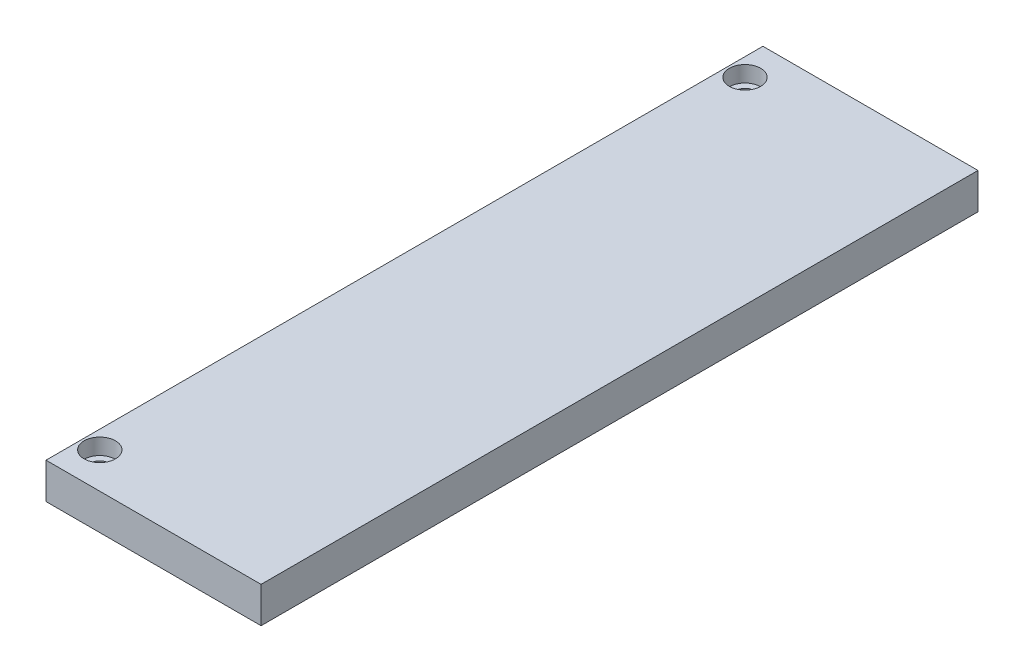
SolidWorks part; units mm, degrees
material "6061 Alloy"
ref_plane "Front Plane" through (0, 0, 0) normal (0, 0, 1) x (1, 0, 0)
ref_plane "Top Plane" through (0, 0, 0) normal (0, 1, 0) x (1, 0, 0)
ref_plane "Right Plane" through (0, 0, 0) normal (1, 0, 0) x (0, 0, -1)
sketch "Sketch1" plane through (0, 0, 0) normal (0, 1, 0) x (1, 0, 0)
  line L1 (-19.05, -63.5) -> (19.05, -63.5)
  line L2 (-19.05, -63.5) -> (-19.05, 63.5)
  line L3 (-19.05, 63.5) -> (19.05, 63.5)
  line L4 (19.05, -63.5) -> (19.05, 63.5)
  line L5 (-19.05, -63.5) -> (19.05, 63.5) construction
  line L6 (-19.05, 63.5) -> (19.05, -63.5) construction
  point P0 (0, 0)
  dimension "D1" = 127
  dimension "D2" = 38.1
extrude "Boss-Extrude1" add sketch "Sketch1" along normal blind 6.35
hole_wizard "CBORE for #4 Socket Head Cap Screw1" positions "Sketch2" profile "Sketch3" counterbore size "#4" standard "ANSI Inch" end condition through all
sketch "Sketch2" plane through (0, 6.35, 0) normal (0, 1, 0) x (1, 0, 0)
  line L0 (19.05, 63.5) -> (-19.05, 63.5) construction
  line L1 (-19.05, 63.5) -> (-19.05, -63.5) construction
  line L2 (-19.05, -63.5) -> (19.05, -63.5) construction
  point P0 (-15.875, -57.15)
  point P2 (-15.875, 57.15)
  dimension "D1" = 6.35
  dimension "D2" = 3.175
  dimension "D3" = 3.175
  dimension "D4" = 6.35
sketch "Sketch3" plane through (-15.875, 6.35, 57.15) normal (1, 0, 0) x (0, 0, 1)
  line L0 (0, 0) -> (0, 6.35)
  line L1 (0, 6.35) -> (1.6319, 6.35)
  line L3 (1.6319, 6.35) -> (1.6319, 2.8448)
  line L4 (1.6319, 2.8448) -> (2.7788, 2.8448)
  line L5 (2.7788, 2.8448) -> (2.7788, 0)
  line L7 (2.7788, 0) -> (0, 0)
  line L11 (0, -6.35) -> (0, 107.95) construction
  dimension "Thru Hole Dia." = 3.2639
  dimension "Thru Hole Depth" = 6.35
  dimension "C'Bore Dia." = 5.5575
  dimension "C'Bore Depth" = 2.8448
